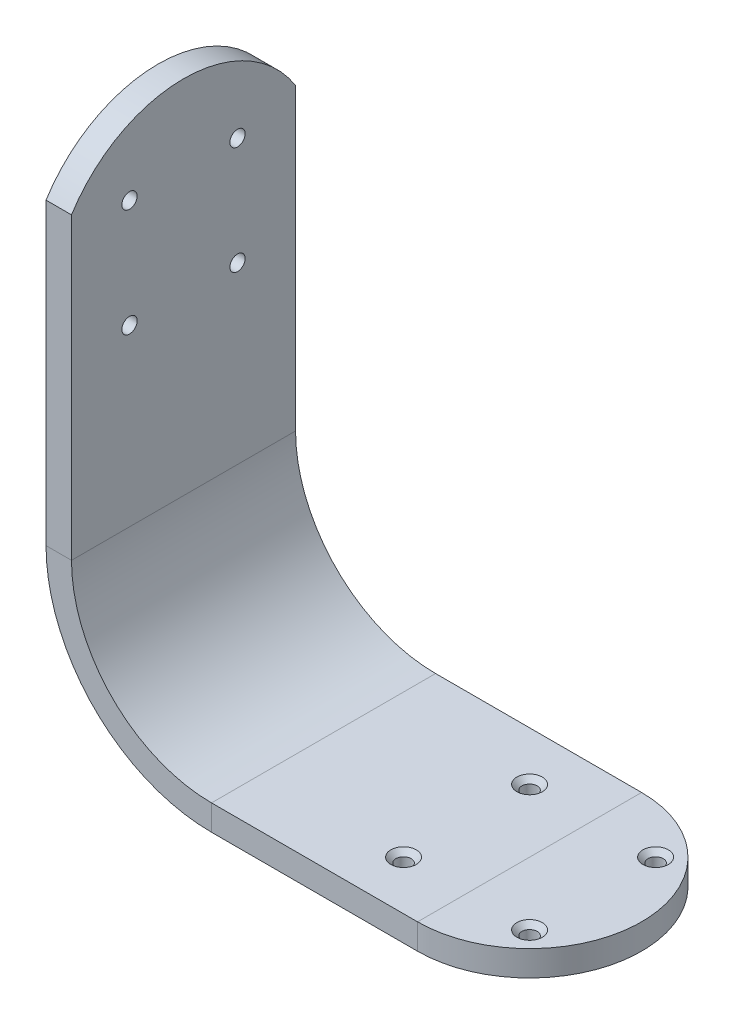
SolidWorks part; units mm, degrees
ref_plane "Спереди" through (0, 0, 0) normal (0, 0, 1) x (1, 0, 0)
ref_plane "Сверху" through (0, 0, 0) normal (0, 1, 0) x (1, 0, 0)
ref_plane "Справа" through (0, 0, 0) normal (1, 0, 0) x (0, 0, -1)
sketch "Эскиз1" plane through (0, 0, 0) normal (0, 0, 1) x (1, 0, 0)
  line L0 (0, 42.8789) -> (0, -28.5217)
  line L1 (30, -58.5217) -> (70.4588, -58.5217)
  line L2 (2.5, 42.3789) -> (2.5, -9.6211) construction
  line L3 (0, 42.8789) -> (3, 42.8789) construction
  line L5 (70.4588, -61.0217) -> (70.4588, -58.5217) construction
  line L6 (70.4588, -58.5217) -> (92.4588, -58.5217)
  arc A0 (0, -28.5217) -> (30, -58.5217) centre (30, -28.5217) ccw
  point P10 (0, 0)
  point P14 (0, 0)
  point P15 (0, 0)
  dimension "D2" = 30
  dimension "D1" = 22
  dimension "D3" = 2.5
  dimension "D4" = 2.5
sketch "Эскиз2" plane through (0, 0, 0) normal (0, 1, 0) x (1, 0, 0)
  line L1 (-2.5, -22) -> (2.5, -22)
  line L2 (-2.5, -22) -> (-2.5, 22)
  line L3 (-2.5, 22) -> (2.5, 22)
  line L4 (2.5, -22) -> (2.5, 22)
  line L5 (-2.5, -22) -> (2.5, 22) construction
  line L6 (-2.5, 22) -> (2.5, -22) construction
  point P0 (0, 0)
  dimension "D1" = 5
  dimension "D2" = 44
sweep "По траектории1" add profiles "Эскиз2" path "Эскиз1"
sketch "Эскиз3" plane through (0, -56.0217, 0) normal (0, 1, 0) x (1, 0, 0)
  line L4 (70.4588, 22) -> (92.4588, 22)
  line L5 (92.4588, 22) -> (92.4588, -22)
  line L6 (92.4588, -22) -> (70.4588, -22)
  arc A0 (70.4588, -22) -> (70.4588, 22) centre (70.4588, 0) ccw
  circle A1 centre (70.4588, 0) radius 43.3473 construction
  line M3 (92.4588, 22) -> (70.4588, 22)
  line M5 (70.4588, -22) -> (92.4588, -22)
  line M6 (92.4588, -22) -> (92.4588, 22)
  dimension "D1" = 44
extrude "Вырез-Вытянуть1" cut sketch "Эскиз3" against normal through all contours A0 L5 M3 | A0 M5 M6 region at (87.5447, -56.0217, 17.0859) region at (87.5447, -56.0217, -17.0859)
sketch "Эскиз4" plane through (-2.5, 0, 0) normal (-1, 0, 0) x (0, 0, 1)
  line L0 (22, -28.5217) -> (22, 42.8789) construction
  line L1 (-22, -28.5217) -> (-22, 42.8789) construction
  line L2 (-22, 42.8789) -> (22, 42.8789) construction
  line L3 (22, -28.5217) -> (22, 2.5225)
  line L4 (-22, -28.5217) -> (-22, 2.5225)
  line L5 (-22, 42.8789) -> (22, 42.8789)
  line L6 (-22, 30.2353) -> (-22, 42.8789)
  line L7 (22, 30.2353) -> (22, 42.8789)
  circle A1 centre (0, 16.3789) radius 26 construction
  arc A2 (-22, 2.5225) -> (22, 2.5225) centre (0, 16.3789) ccw
  arc A3 (22, 30.2353) -> (-22, 30.2353) centre (0, 16.3789) ccw
  line M2 (22, -28.5217) -> (22, 42.8789)
  line M3 (22, 42.8789) -> (-22, 42.8789)
  line M4 (-22, 42.8789) -> (-22, -28.5217)
extrude "Вырез-Вытянуть2" cut sketch "Эскиз4" against normal through all contours A3 M2 M3 M4 region at (-2.5, 42.4211, 0)
sketch "Эскиз5" plane through (0, -56.0217, 0) normal (0, 1, 0) x (1, 0, 0)
  circle A3 centre (82.8332, 12.3744) radius 1.5 construction
  circle A4 centre (82.8332, -12.3744) radius 1.5 construction
  circle A5 centre (58.0845, -12.3744) radius 1.5 construction
  circle A6 centre (58.0845, 12.3744) radius 1.5 construction
  circle A7 centre (82.8332, 12.3744) radius 1.5
  circle A8 centre (82.8332, -12.3744) radius 1.5
  circle A9 centre (58.0845, -12.3744) radius 1.5
  circle A10 centre (58.0845, 12.3744) radius 1.5
hole_wizard "Зенковка для  винта с потайной головкой с внутренним шестигранником M31" positions "Эскиз6" profile "Эскиз7" countersink size "M3" standard "Ansi Metric" end condition through all
sketch "Эскиз6" plane through (0, -56.0217, 0) normal (0, 1, 0) x (1, 0, 0)
  point P0 (58.0845, -12.3744)
  point P3 (82.8332, -12.3744)
  point P6 (82.8332, 12.3744)
  point P9 (58.0845, 12.3744)
sketch "Эскиз7" plane through (58.0845, -56.0217, 12.3744) normal (1, 0, 0) x (0, 0, 1)
  line L0 (0, 0) -> (0, 5)
  line L1 (0, 5) -> (1.5, 5)
  line L2 (1.5, 5) -> (1.5, 1)
  line L3 (1.5, 1) -> (2.5, 0)
  line L5 (2.5, 0) -> (0, 0)
  line L6 (-1.5, 1) -> (-2.5, 0) construction
  line L11 (0, -6.35) -> (0, 107.95) construction
  dimension "Диаметр сквозного отверстия" = 3
  dimension "Глубина сквозного отверстия" = 5
  dimension "Диаметр передней зенковки" = 5
  dimension "Угол передней зенковки" = 90
sketch "Эскиз8" plane through (-2.5, 0, 0) normal (-1, 0, 0) x (0, 0, 1)
  circle A0 centre (10.6066, 5.7723) radius 1.5 construction
  circle A1 centre (-10.6066, 5.7723) radius 1.5 construction
  circle A2 centre (-10.6066, 26.9855) radius 1.5 construction
  circle A3 centre (10.6066, 26.9855) radius 1.5 construction
  circle A4 centre (10.6066, 5.7723) radius 1.5
  circle A5 centre (-10.6066, 5.7723) radius 1.5
  circle A6 centre (-10.6066, 26.9855) radius 1.5
  circle A7 centre (10.6066, 26.9855) radius 1.5
hole_wizard "Цековка для винта с внутренним шестигранником M31" positions "Эскиз9" profile "Эскиз10" counterbore size "M3" standard "Ansi Metric" end condition through all
sketch "Эскиз9" plane through (-2.5, 0, 0) normal (-1, 0, 0) x (0, 0, 1)
  point P0 (-10.6066, 26.9855)
  point P3 (10.6066, 26.9855)
  point P6 (-10.6066, 5.7723)
  point P9 (10.6066, 5.7723)
sketch "Эскиз10" plane through (-2.5, 26.9855, -10.6066) normal (0, 1, 0) x (0, 0, 1)
  line L0 (0, 0) -> (0, 94.9588)
  line L1 (0, 94.9588) -> (1.5, 94.9588)
  line L3 (1.5, 94.9588) -> (1.5, 1.5)
  line L4 (2.75, 1.5) -> (1.5, 1.5)
  line L5 (2.75, 1.5) -> (2.75, 0.525)
  line L6 (2.75, 0.525) -> (3.275, 0)
  line L7 (3.275, 0) -> (0, 0)
  line L8 (-2.75, 0.525) -> (-3.275, 0) construction
  line L11 (0, -6.35) -> (0, 107.95) construction
  dimension "Диаметр сквозного отверстия" = 3
  dimension "Глубина сквозного отверстия" = 94.9588
  dimension "Диаметр цековки" = 5.5
  dimension "Глубина цековки" = 1.5
  dimension "Диаметр передней зенковки" = 6.55
  dimension "Угол передней зенковки" = 90
